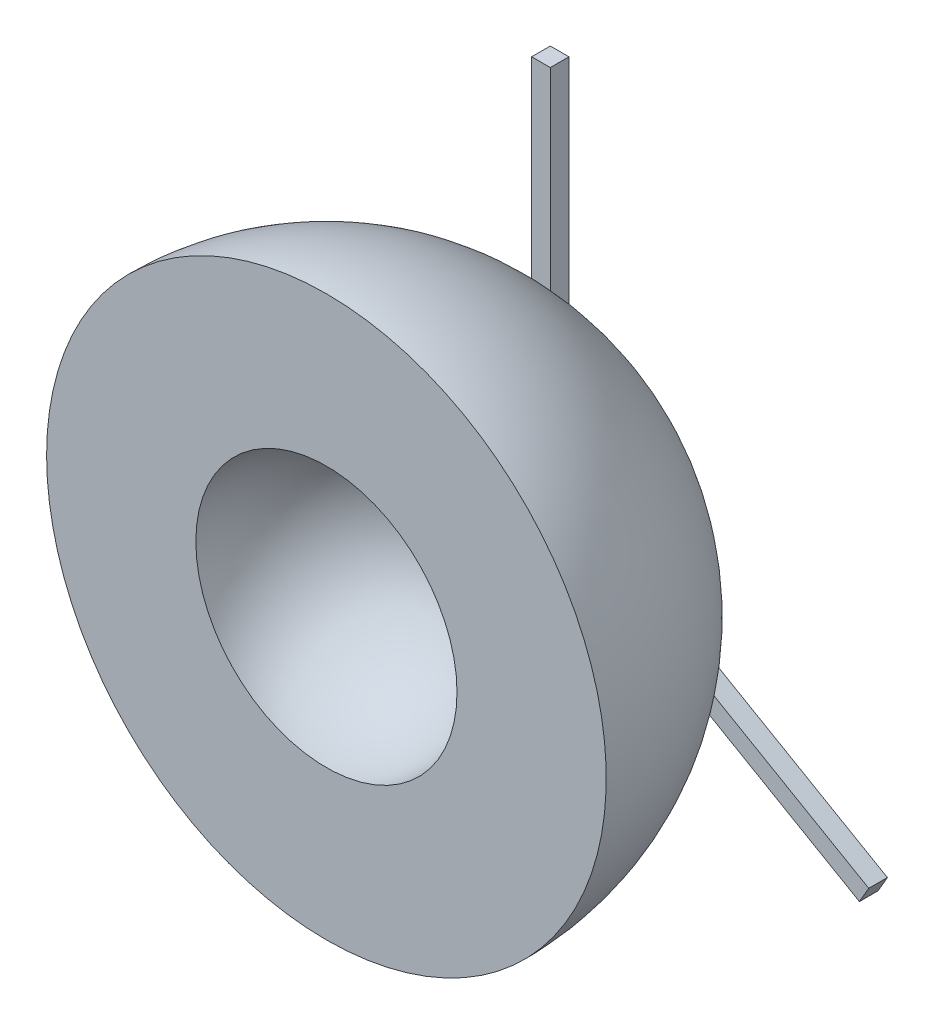
SolidWorks part; units mm, degrees
ref_plane "正面" through (0, 0, 0) normal (0, 0, 1) x (1, 0, 0)
ref_plane "平面" through (0, 0, 0) normal (0, 1, 0) x (1, 0, 0)
ref_plane "右側面" through (0, 0, 0) normal (1, 0, 0) x (0, 0, -1)
sketch "ｽｹｯﾁ1" plane through (0, 0, 0) normal (0, 0, 1) x (1, 0, 0)
  line L0 (0, 150) -> (0, -150)
  arc A0 (0, 150) -> (0, -150) centre (0, 0) ccw
  arc A1 (0, 70) -> (0, -70) centre (0, 0) ccw
  dimension "D1" = 150
  dimension "D2" = 70
revolve "回転1" add sketch "ｽｹｯﾁ1" angle 180 about L0 region at (-73.1148, 0, 0)
sketch "ｽｹｯﾁ2" plane through (0, 0, 0) normal (0, 1, 0) x (1, 0, 0)
  line L1 (-5, 115) -> (5, 115)
  line L2 (-5, 115) -> (-5, 125)
  line L3 (-5, 125) -> (5, 125)
  line L4 (5, 115) -> (5, 125)
  line L5 (-5, 115) -> (5, 125) construction
  line L6 (-5, 125) -> (5, 115) construction
  point P0 (0, 120)
  dimension "D1" = 120
  dimension "D2" = 10
  dimension "D3" = 10
extrude "ﾎﾞｽ - 押し出し1" add sketch "ｽｹｯﾁ2" along normal blind 200
ref_axis "軸1" through (0, 0, 7.5) along (0, 0, -1)
ref_plane "平面1" through (0, 0, 0) normal (0.866, -0.5, 0) x (0, 0, -1)
sketch "ｽｹｯﾁ5" plane through (0, 0, 0) normal (0.866, -0.5, 0) x (0, 0, -1)
  line L1 (115, -5) -> (125, -5)
  line L2 (115, -5) -> (115, 5)
  line L3 (115, 5) -> (125, 5)
  line L4 (125, -5) -> (125, 5)
  line L5 (115, -5) -> (125, 5) construction
  line L6 (115, 5) -> (125, -5) construction
  point P0 (120, 0)
  dimension "D1" = 120
  dimension "D2" = 10
  dimension "D3" = 10
extrude "ﾎﾞｽ - 押し出し3" add sketch "ｽｹｯﾁ5" along normal blind 200
ref_plane "平面2" through (0, 0, 0) normal (-0.866, -0.5, 0) x (0, 0, -1)
sketch "ｽｹｯﾁ6" plane through (0, 0, 0) normal (-0.866, -0.5, 0) x (0, 0, -1)
  line L0 (-7.5, 0) -> (157.5, 0) construction
  line L1 (125, 5) -> (115, 5)
  line L2 (125, 5) -> (125, -5)
  line L3 (125, -5) -> (115, -5)
  line L4 (115, 5) -> (115, -5)
  line L5 (125, 5) -> (115, -5) construction
  line L6 (125, -5) -> (115, 5) construction
  point P0 (120, 0)
  point P9 (0, 0)
  dimension "D1" = 10
  dimension "D2" = 10
  dimension "D3" = 0
  dimension "D4" = 120
extrude "ﾎﾞｽ - 押し出し4" add sketch "ｽｹｯﾁ6" along normal blind 200
